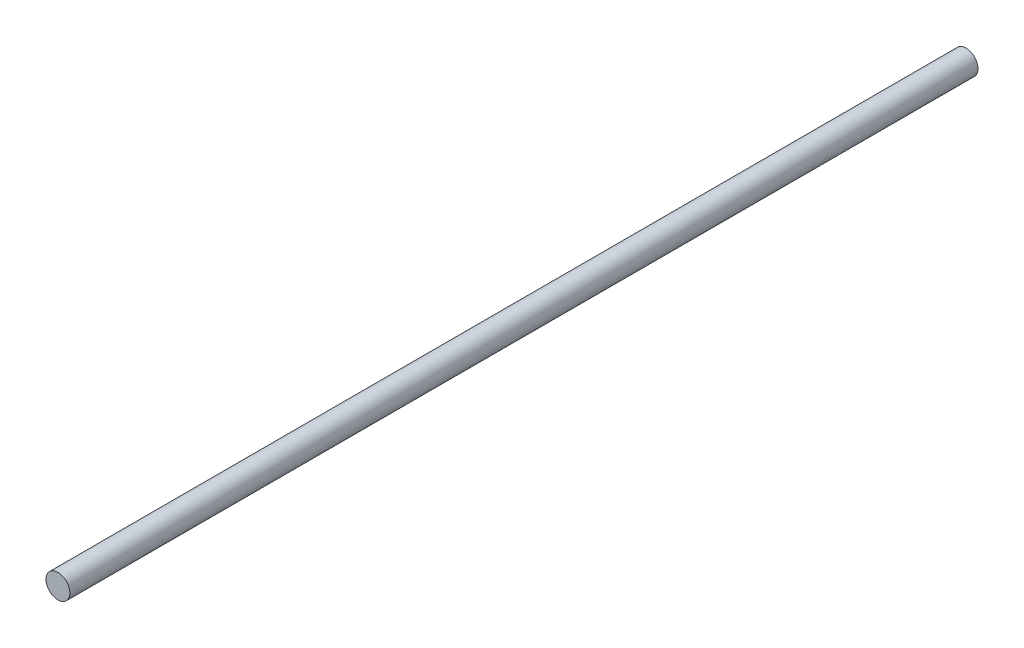
SolidWorks part; units mm, degrees
ref_plane "Front Plane" through (0, 0, 0) normal (0, 0, 1) x (1, 0, 0)
ref_plane "Top Plane" through (0, 0, 0) normal (0, 1, 0) x (1, 0, 0)
ref_plane "Right Plane" through (0, 0, 0) normal (1, 0, 0) x (0, 0, -1)
sketch "base" plane through (0, 0, 0) normal (0, 0, 1) x (1, 0, 0)
  circle A0 centre (0, 0) radius 50
  arc A4 (10, 48.9898) -> (-10, 48.9898) centre (0, 0) ccw construction
extrude "Boss-Extrude1" add sketch "base" along normal blind 2800 and the other way blind 1000
sketch "center" plane through (0, 0, 0) normal (0, 1, 0) x (1, 0, 0)
  line L0 (0, -2800) -> (0, 1000) construction
  line L1 (-50, -2800) -> (50, -2800) construction
  line L2 (50, 1000) -> (-50, 1000) construction
